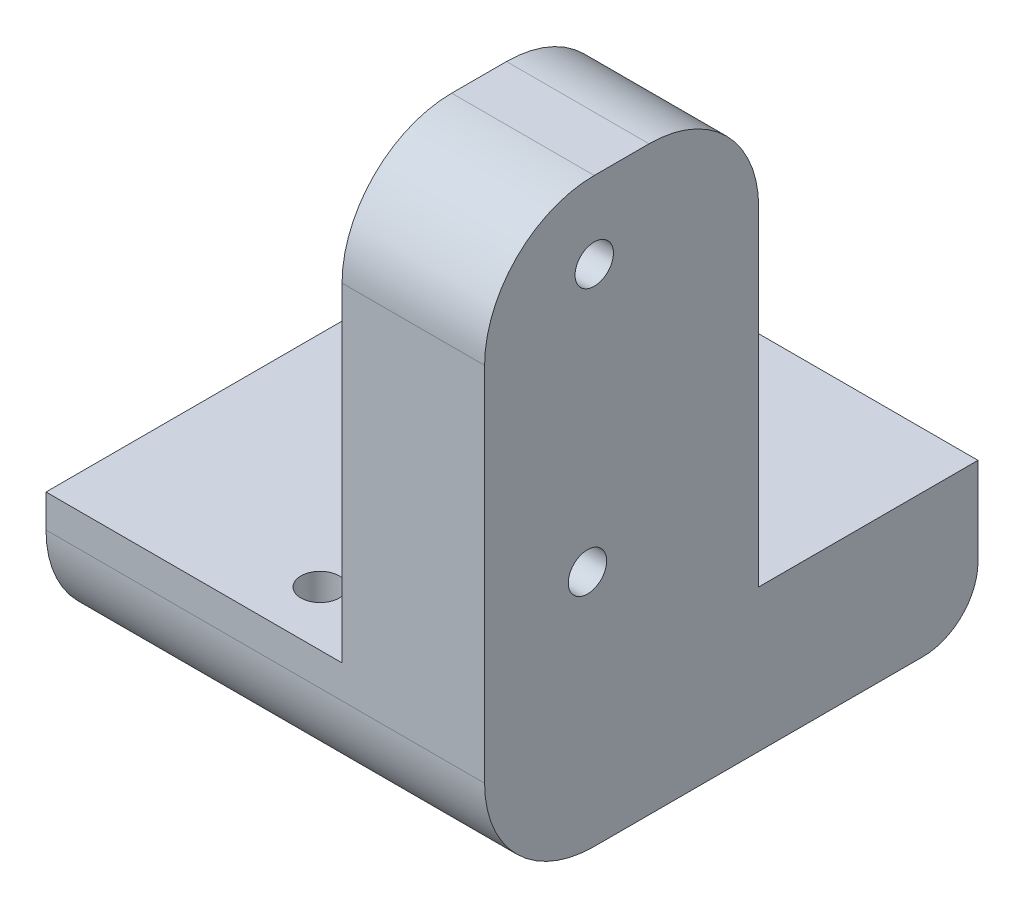
SolidWorks part; units mm, degrees
ref_plane "Front Plane" through (0, 0, 0) normal (0, 0, 1) x (1, 0, 0)
ref_plane "Top Plane" through (0, 0, 0) normal (0, 1, 0) x (1, 0, 0)
ref_plane "Right Plane" through (0, 0, 0) normal (1, 0, 0) x (0, 0, -1)
sketch "Sketch1" plane through (0, 0, 0) normal (0, 1, 0) x (1, 0, 0)
  line L1 (-20, 25) -> (20, 25)
  line L2 (-20, 25) -> (-20, -25)
  line L3 (-20, -25) -> (20, -25)
  line L4 (20, 25) -> (20, -25)
  dimension "D1" = 40
  dimension "D2" = 50
  dimension "D3" = 25
  dimension "D4" = 20
extrude "Boss-Extrude1" add sketch "Sketch1" along normal blind 13
sketch "Sketch2" plane through (0, 13, 0) normal (0, 1, 0) x (1, 0, 0)
  line L1 (20, -25) -> (7, -25)
  line L2 (20, -25) -> (20, 5)
  line L3 (20, 5) -> (7, 5)
  line L4 (7, -25) -> (7, 5)
  dimension "D1" = 13
  dimension "D2" = 30
extrude "Boss-Extrude2" add sketch "Sketch2" along normal blind 40
sketch "Sketch3" plane through (20, 0, 0) normal (1, 0, 0) x (0, 0, -1)
  line L0 (-25, 53) -> (5, 53) construction
  line L1 (5, 53) -> (5, 13) construction
  circle A0 centre (-10, 46) radius 1.75
  circle A1 centre (-10.6168, 22) radius 1.75
  dimension "D1" = 3.5
  dimension "D2" = 3.5
  dimension "D3" = 24
  dimension "D4" = 7
  dimension "D5" = 15
extrude "Cut-Extrude1" cut sketch "Sketch3" against normal blind 32
sketch "Sketch4" plane through (0, 0, 0) normal (0, -1, 0) x (-1, 0, 0)
  line L0 (20, -25) -> (-20, -25) construction
  line L1 (13, -25) -> (-13, -25)
  line L2 (13, -25) -> (13, 25)
  line L3 (13, 25) -> (-13, 25)
  line L4 (-13, -25) -> (-13, 25)
  line L5 (-20, 25) -> (20, 25) construction
  dimension "D1" = 26
  dimension "D2" = 13
extrude "Cut-Extrude2" cut sketch "Sketch4" against normal blind 3
sketch "Sketch5" plane through (0, 3, 0) normal (0, -1, 0) x (-1, 0, 0)
  circle A0 centre (0, 0) radius 1.75
  circle A1 centre (0, -15) radius 1.75
  circle A3 centre (0, 15) radius 1.75
  dimension "D1" = 3.5
  dimension "D2" = 3.5
  dimension "D4" = 3.5
  dimension "D5" = 15
  dimension "D6" = 15
extrude "Cut-Extrude3" cut sketch "Sketch5" against normal blind 10
sketch "Sketch6" plane through (0, 0, 25) normal (0, 0, 1) x (1, 0, 0)
  line L1 (20, 53) -> (-20, 53)
  line L2 (20, 53) -> (20, 0)
  line L3 (20, 0) -> (-20, 0)
  line L4 (-20, 53) -> (-20, 0)
extrude "Cut-Extrude4" cut sketch "Sketch6" against normal blind 5
fillet "Fillet1" radius 10 1 edges at (13.5, 53, 20)
fillet "Fillet2" radius 10 1 edges at (13.5, 53, -5)
fillet "Fillet3" radius 10 1 edges at (-16.5, 0, 20)
fillet "Fillet4" radius 5 1 edges at (-16.5, 0, -25)
sketch "Sketch7" plane through (7, 0, 0) normal (-1, 0, 0) x (0, 0, 1)
  circle A0 centre (10.6168, 22) radius 3.5
  circle A1 centre (10, 46) radius 3.5
  dimension "D1" = 7
  dimension "D2" = 7
extrude "Cut-Extrude5" cut sketch "Sketch7" against normal blind 5
